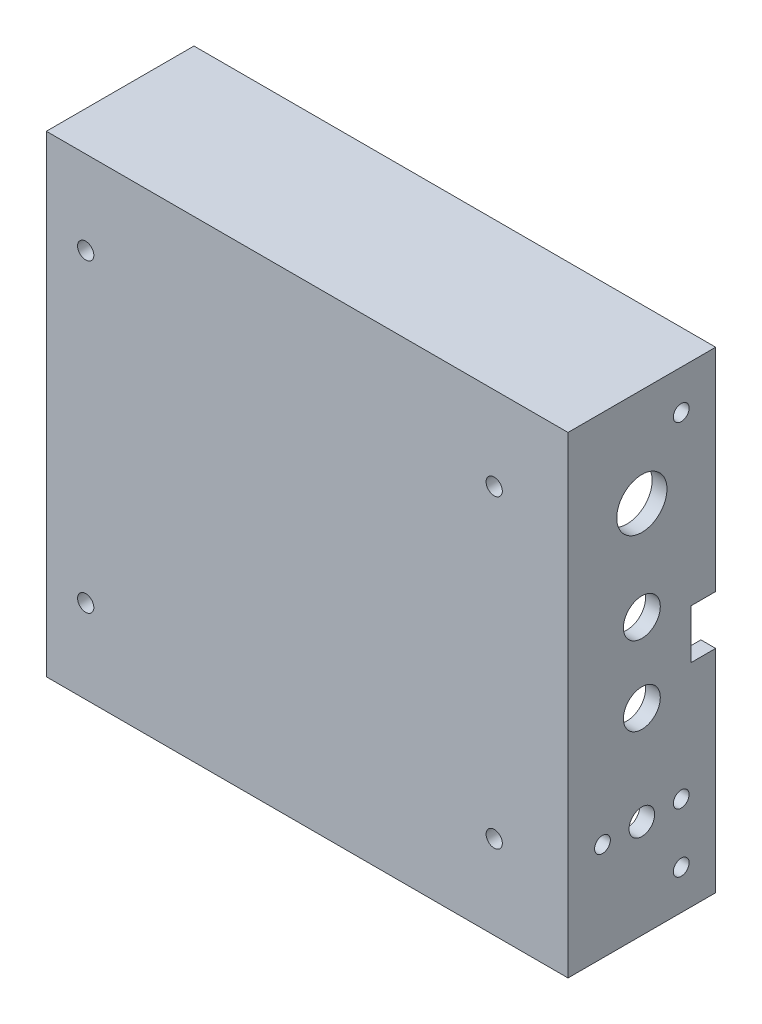
SolidWorks part; units mm, degrees
ref_plane "Front Plane" through (0, 0, 0) normal (0, 0, 1) x (1, 0, 0)
ref_plane "Top Plane" through (0, 0, 0) normal (0, 1, 0) x (1, 0, 0)
ref_plane "Right Plane" through (0, 0, 0) normal (1, 0, 0) x (0, 0, -1)
sketch "Sketch1" plane through (0, 0, 0) normal (0, 0, 1) x (1, 0, 0)
  line L1 (-50, -45) -> (50, -45)
  line L2 (-50, -45) -> (-50, 45)
  line L3 (-50, 45) -> (50, 45)
  line L4 (50, -45) -> (50, 45)
  line L5 (-50, -45) -> (50, 45) construction
  line L6 (-50, 45) -> (50, -45) construction
  line L7 (-45, -31) -> (38, -31)
  line L8 (-45, -31) -> (-45, 31)
  line L9 (-45, 31) -> (38, 31)
  line L10 (38, -31) -> (38, 31)
  line L11 (-45, -31) -> (38, 31) construction
  line L12 (-45, 31) -> (38, -31) construction
  circle A0 centre (-45, 31) radius 1.65
  circle A1 centre (38, 31) radius 1.65
  circle A2 centre (38, -31) radius 1.65
  circle A3 centre (-45, -31) radius 1.65
  point P0 (0, 0)
  point P6 (-3.5, 0)
  dimension "D7" = 3.3
  dimension "D1" = 90
  dimension "D2" = 100
  dimension "D3" = 62
  dimension "D4" = 83
  dimension "D5" = 14
  dimension "D6" = 5
extrude "Boss-Extrude2" add sketch "Sketch1" along normal blind 3 contours L1 L4 L3 L2 A3 L8 A0 L9 A1 L10 A2 L7 | A3 L7 A2 L10 A1 L9 A0 L8 region at (-48.6546, 0, 0) region at (-3.5, 0, 0)
sketch "Sketch2" plane through (0, 0, 3) normal (0, 0, 1) x (1, 0, 0)
  line L1 (50, -45) -> (-50, -45)
  line L2 (50, -45) -> (50, 45)
  line L3 (50, 45) -> (-50, 45)
  line L4 (-50, -45) -> (-50, 45)
  line L5 (50, -45) -> (-50, 45) construction
  line L6 (50, 45) -> (-50, -45) construction
  line L7 (53, -48) -> (-53, -48)
  line L8 (53, -48) -> (53, 48)
  line L9 (53, 48) -> (-53, 48)
  line L10 (-53, -48) -> (-53, 48)
  line L11 (53, -48) -> (-53, 48) construction
  line L12 (53, 48) -> (-53, -48) construction
  point P0 (0, 0)
  point P7 (0, 0)
  dimension "D1" = 3
  dimension "D2" = 3
extrude "Boss-Extrude3" add sketch "Sketch2" against normal blind 30
sketch "Sketch3" plane through (-53, 0, 0) normal (-1, 0, 0) x (0, 0, 1)
  line L0 (-27, 48) -> (-27, -48) construction
  line L1 (-27, 48) -> (3, 48) construction
  line L2 (-27, -48) -> (3, -48) construction
  circle A0 centre (-20, -40) radius 1.6
  circle A1 centre (-20, 40) radius 1.6
  dimension "D1" = 3.2
  dimension "D2" = 7
  dimension "D3" = 8
  dimension "D4" = 8
  dimension "D5" = 7
  dimension "D6" = 3.2
extrude "Cut-Extrude1" cut sketch "Sketch3" against normal up to surface (106 mm away) up to face at (53, 0, -12)
sketch "Sketch4" plane through (53, 0, 0) normal (1, 0, 0) x (0, 0, -1)
  line L0 (27, -48) -> (27, 48) construction
  line L1 (27, 5) -> (22, 5)
  line L2 (27, 5) -> (27, -5)
  line L3 (27, -5) -> (22, -5)
  line L4 (22, 5) -> (22, -5)
  line L5 (27, -48) -> (-3, -48) construction
  line L6 (27, 48) -> (-3, 48) construction
  line L7 (-3, -48) -> (-3, 48) construction
  circle A0 centre (12, -8) radius 3.75
  circle A1 centre (12, 8) radius 3.75
  dimension "D4" = 7.5
  dimension "D5" = 7.5
  dimension "D6" = 15
  dimension "D7" = 40
  dimension "D8" = 40
  dimension "D9" = 15
  dimension "D1" = 5
  dimension "D2" = 10
  dimension "D3" = 43
extrude "Cut-Extrude3" cut sketch "Sketch4" against normal blind 10
sketch "Sketch5" plane through (53, 0, 0) normal (1, 0, 0) x (0, 0, -1)
  line L0 (27, 5) -> (27, 48) construction
  line L1 (27, 48) -> (-3, 48) construction
  circle A0 centre (12, 28) radius 5.1
  dimension "D1" = 10.2
  dimension "D2" = 15
  dimension "D3" = 20
extrude "Cut-Extrude4" cut sketch "Sketch5" against normal blind 10
sketch "Sketch6" plane through (53, 0, 0) normal (1, 0, 0) x (0, 0, -1)
  line L0 (20, -28) -> (4, -28)
  line L3 (27, -48) -> (-3, -48) construction
  line L4 (-3, -48) -> (-3, 48) construction
  circle A0 centre (12, -28) radius 2.6
  circle A1 centre (4, -28) radius 1.6
  circle A2 centre (20, -28) radius 1.6
  point P3 (12, -28)
  dimension "D4" = 3.2
  dimension "D5" = 5.2
  dimension "D1" = 16
  dimension "D2" = 15
  dimension "D3" = 20
extrude "Cut-Extrude5" cut sketch "Sketch6" against normal blind 10 contours L0 A0 | A0 | A1 | A2 region at (53, -29.1035, -12)
